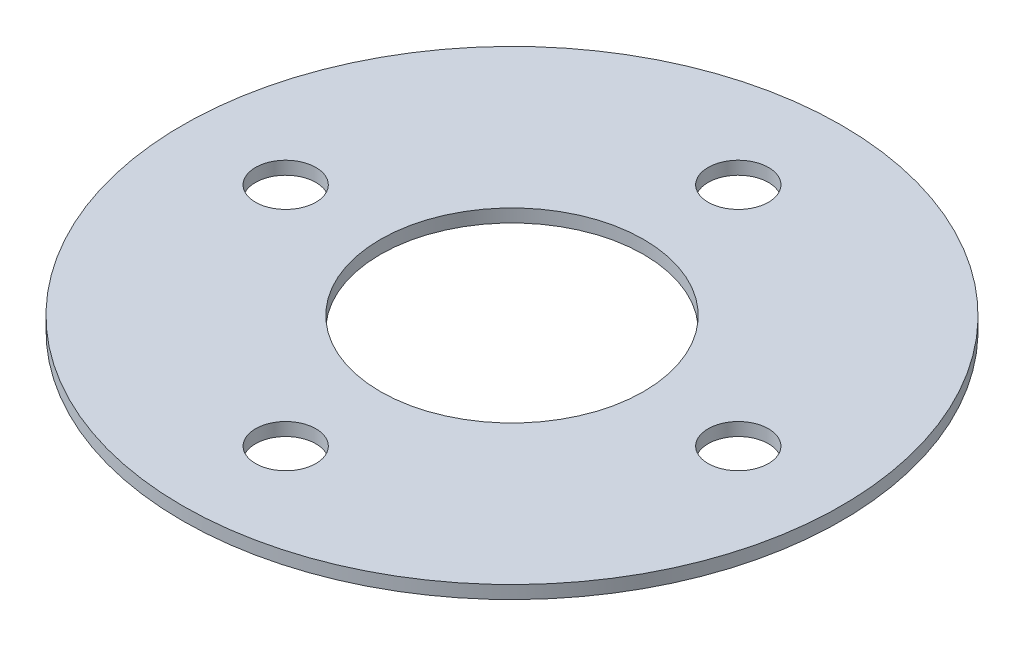
SolidWorks part; units mm, degrees
material "201 Annealed Stainless Steel (SS)"
ref_plane "Front Plane" through (0, 0, 0) normal (0, 0, 1) x (1, 0, 0)
ref_plane "Top Plane" through (0, 0, 0) normal (0, 1, 0) x (1, 0, 0)
ref_plane "Right Plane" through (0, 0, 0) normal (1, 0, 0) x (0, 0, -1)
sketch "Sketch1" plane through (0, 0, 0) normal (0, 1, 0) x (1, 0, 0)
  circle A0 centre (0, 0) radius 21.844
  circle A1 centre (0, 15) radius 2
  circle A2 centre (15, 0) radius 2
  circle A3 centre (0, -15) radius 2
  circle A4 centre (-15, 0) radius 2
  point P14 (0, 0)
  dimension "D1" = 43.688
  dimension "D2" = 4
  dimension "D3" = 15
  dimension "D4" = 4
extrude "Boss-Extrude1" add sketch "Sketch1" along normal blind 0.8636
sketch "Sketch2" plane through (0, 0, 0) normal (0, -1, 0) x (1, 0, 0)
  circle A0 centre (0, 0) radius 8.7312
  dimension "D1" = 17.4625
extrude "Cut-Extrude1" cut sketch "Sketch2" against normal blind 0.8636
